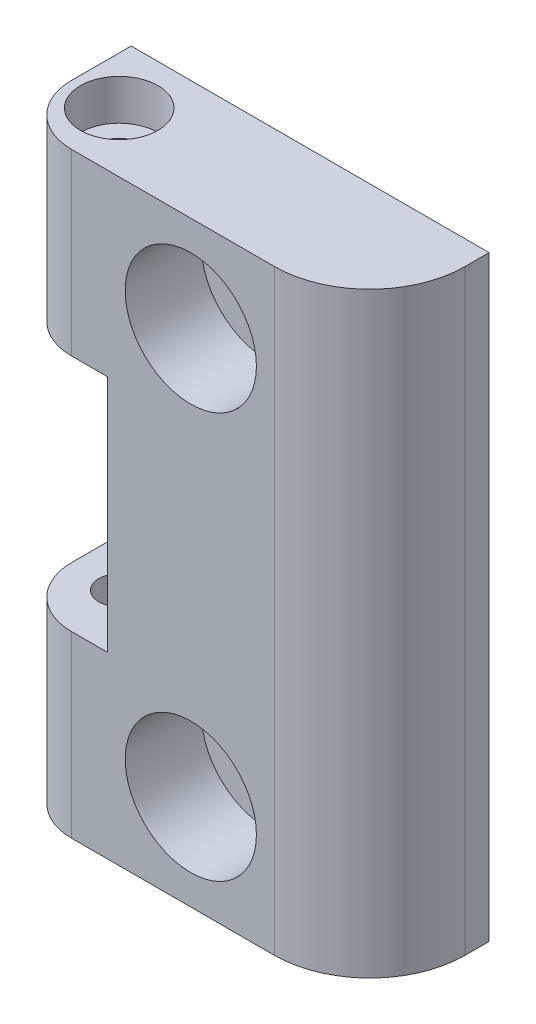
SolidWorks part; units mm, degrees
ref_plane "Přední rovina" through (0, 0, 0) normal (0, 0, 1) x (1, 0, 0)
ref_plane "Horní rovina" through (0, 0, 0) normal (0, 1, 0) x (1, 0, 0)
ref_plane "Pravá rovina" through (0, 0, 0) normal (1, 0, 0) x (0, 0, -1)
sketch "Base sketch" plane through (0, 0, 0) normal (0, 0, 1) x (1, 0, 0)
  line L0 (-15, 10) -> (-7, 10)
  line L1 (-15, 25) -> (15, 25)
  line L2 (-15, 25) -> (-15, -25)
  line L3 (-15, -25) -> (15, -25)
  line L4 (15, 25) -> (15, -25)
  line L5 (-15, 25) -> (15, -25) construction
  line L6 (-15, -25) -> (15, 25) construction
  line L7 (-7, 10) -> (-7, -10)
  line L8 (-7, -10) -> (-15, -10)
  point P0 (0, 0)
  dimension "D1" = 50
  dimension "D2" = 30
  dimension "D3" = 15
  dimension "D4" = 15
  dimension "D5" = 8
extrude "Base" add sketch "Base sketch" along normal blind 10 contours L7 L8 L2 L3 L4 L1 L0 region at (1.3134, 0, 0)
sketch "Mount holes sketch" plane through (0, 0, 10) normal (0, 0, 1) x (1, 0, 0)
  line L0 (0, 25) -> (0, -25)
  line L1 (-15, 25) -> (15, 25) construction
  line L2 (-15, -25) -> (15, -25) construction
  point P6 (0, 17)
  point P7 (0, -17)
  dimension "D1" = 8
  dimension "D2" = 8
hole_wizard "Mount holes" positions "Skica3" profile "Skica4" counterbore size "M6" standard "DIN" end condition through all
sketch "Skica3" plane through (0, 0, 10) normal (0, 0, 1) x (1, 0, 0)
  point P0 (0, 17)
  point P3 (0, -17)
sketch "Skica4" plane through (0, 17, 10) normal (1, 0, 0) x (0, -1, 0)
  line L0 (0, 0) -> (0, 10)
  line L1 (0, 10) -> (3.3, 10)
  line L3 (3.3, 10) -> (3.3, 6.4)
  line L4 (3.3, 6.4) -> (5.5, 6.4)
  line L5 (5.5, 6.4) -> (5.5, 0)
  line L7 (5.5, 0) -> (0, 0)
  line L11 (0, -6.35) -> (0, 107.95) construction
  dimension "Průměr díry skrz" = 6.6
  dimension "Hloubka díry skrz" = 10
  dimension "Průměr válcového zahloubení" = 11
  dimension "Hloubka válcového zahloubení" = 6.4
sketch "Top screw sketch" plane through (0, 25, 0) normal (0, 1, 0) x (1, 0, 0)
  line L0 (-15, -5) -> (15, -5)
  line L1 (-15, -10) -> (-15, 0) construction
  line L2 (15, -10) -> (15, 0) construction
  point P6 (-11, -5)
  dimension "D1" = 4
hole_wizard "Top hinge" positions "Skica6" profile "Skica7" counterbore size "M3" standard "DIN" end condition up to next
sketch "Skica6" plane through (0, 25, 0) normal (0, 1, 0) x (1, 0, 0)
  point P0 (-11, -5)
sketch "Skica7" plane through (-11, 25, 5) normal (1, 0, 0) x (0, 0, 1)
  line L0 (0, 0) -> (0, 15)
  line L1 (0, 15) -> (1.7, 15)
  line L3 (1.7, 15) -> (1.7, 3.4)
  line L4 (1.7, 3.4) -> (3.25, 3.4)
  line L5 (3.25, 3.4) -> (3.25, 0)
  line L7 (3.25, 0) -> (0, 0)
  line L11 (0, -6.35) -> (0, 107.95) construction
  dimension "Průměr díry skrz" = 3.4
  dimension "Hloubka díry skrz" = 15
  dimension "Průměr válcového zahloubení" = 6.5
  dimension "Hloubka válcového zahloubení" = 3.4
sketch "Bottom screw sketch" plane through (0, -25, 0) normal (0, -1, 0) x (1, 0, 0)
  line L0 (-15, 5) -> (15, 5)
  line L1 (-15, 10) -> (-15, 0) construction
  line L2 (15, 10) -> (15, 0) construction
  point P6 (-11, 5)
  dimension "D1" = 4
hole_wizard "Bottom hinge" positions "Skica9" profile "Skica10" counterbore size "M3" standard "DIN" end condition up to next
sketch "Skica9" plane through (0, -25, 0) normal (0, -1, 0) x (-1, 0, 0)
  point P0 (11, -5)
sketch "Skica10" plane through (-11, -25, 5) normal (1, 0, 0) x (0, 0, -1)
  line L0 (0, 0) -> (0, 15)
  line L1 (0, 15) -> (1.7, 15)
  line L3 (1.7, 15) -> (1.7, 8)
  line L4 (1.7, 8) -> (1.9, 8)
  line L5 (1.9, 8) -> (1.9, 0)
  line L7 (1.9, 0) -> (0, 0)
  line L11 (0, -6.35) -> (0, 107.95) construction
  dimension "Průměr díry skrz" = 3.4
  dimension "Hloubka díry skrz" = 15
  dimension "Průměr válcového zahloubení" = 3.8
  dimension "Hloubka válcového zahloubení" = 8
sketch "profile sketch" plane through (0, 0, 0) normal (0, 0, -1) x (-1, 0, 0)
  line L0 (15, -25) -> (-15, -25) construction
  line L1 (-4, 25) -> (4, 25)
  line L2 (-4, 25) -> (-4, -25)
  line L3 (-4, -25) -> (4, -25)
  line L4 (4, 25) -> (4, -25)
  line L5 (-4, 25) -> (4, -25) construction
  line L6 (-4, -25) -> (4, 25) construction
  circle A0 centre (0, -17) radius 8
  circle A1 centre (0, 17) radius 8
  point P0 (0, 0)
  dimension "D2" = 16
  dimension "D1" = 8
extrude "Profile click" add sketch "profile sketch" along normal blind 3 contours A1 L2 A0 L4 region at (0, 0, 0)
fillet "Hinge round" radius 5 2 edges at (-15, -17.5, 10) (-15, 17.5, 10)
fillet "Zaoblit2" radius 8 1 edges at (15, 0, 10)
